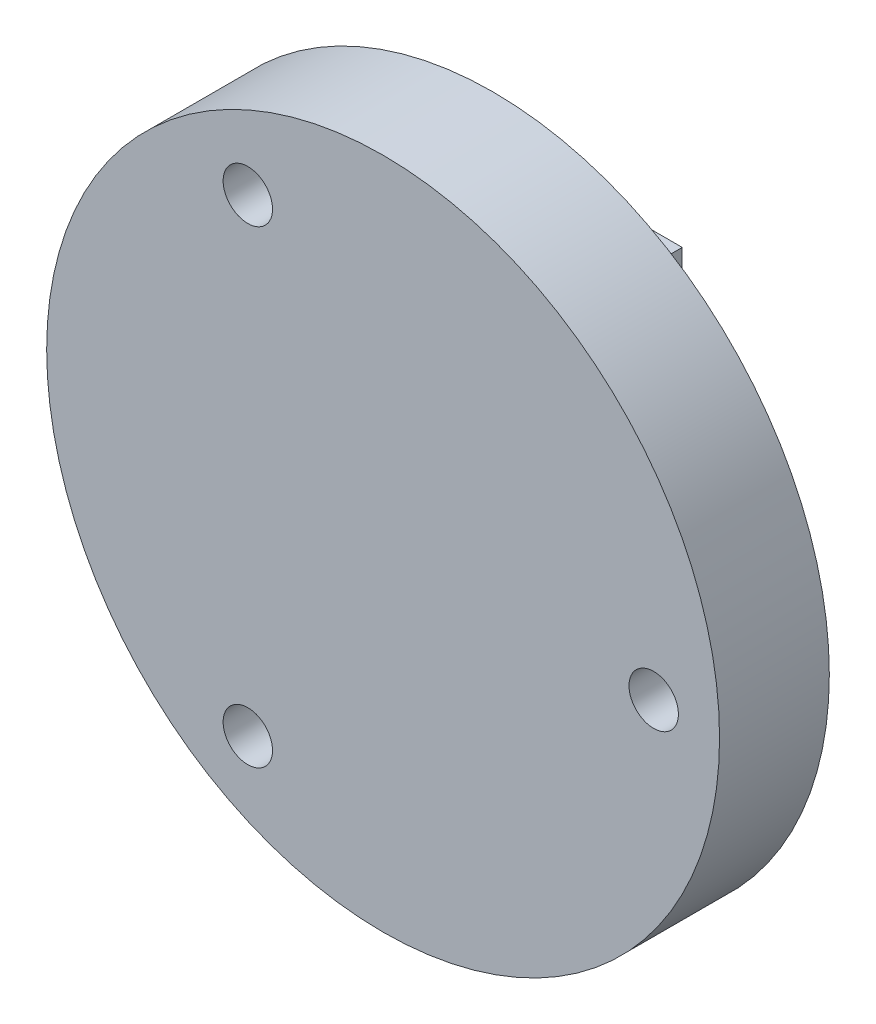
SolidWorks part; units mm, degrees
ref_plane "Спереди" through (0, 0, 0) normal (0, 0, 1) x (1, 0, 0)
ref_plane "Сверху" through (0, 0, 0) normal (0, 1, 0) x (1, 0, 0)
ref_plane "Справа" through (0, 0, 0) normal (1, 0, 0) x (0, 0, -1)
sketch "Эскиз основы" plane through (0, 0, 0) normal (0, 0, 1) x (1, 0, 0)
  line L0 (0, 0) -> (24.65, 0) construction
  line L1 (0, 0) -> (30.65, 0) construction
  line L2 (5.25, -15) -> (-5.25, -15)
  line L3 (5.25, -15) -> (5.25, 15)
  line L4 (5.25, 15) -> (-5.25, 15)
  line L5 (-5.25, -15) -> (-5.25, 15)
  line L6 (5.25, -15) -> (-5.25, 15) construction
  line L7 (5.25, 15) -> (-5.25, -15) construction
  circle A0 centre (0, 0) radius 30.65
  circle A2 centre (0, 0) radius 24.65
  circle A3 centre (24.65, 0) radius 2.25
  circle A4 centre (24.65, 0) radius 3.55
  circle A5 centre (-12.325, -21.3475) radius 3.55
  circle A6 centre (-12.325, -21.3475) radius 2.25
  circle A7 centre (-12.325, 21.3475) radius 3.55
  circle A8 centre (-12.325, 21.3475) radius 2.25
  point P14 (0, 0)
  point P18 (0, 0)
  dimension "D1" = 10.5
  dimension "D2" = 61.3
  dimension "D3" = 49.3
  dimension "D4" = 7.1
  dimension "D5" = 4.5
  dimension "D6" = 24.65
  dimension "D8" = 30
  dimension "D7" = 3
extrude "Основа" add sketch "Эскиз основы" along normal blind 10 contours A0 A7 A2 A4 A5 | A8 A2 A7 | A2 A4 A3 | A2 A4 A3 | A6 A2 A5 | A6 A2 A5 | A7 A2 A5 A4 L2 L5 L4 L3 | L5 L2 L3 L4 | A8 A2 A7 region at (0, 0, 0) region at (-29.7831, 0, 0) region at (22.3212, 0, 0) region at (24.5594, 2.9047, 0) region at (20.4046, 0, 0) region at (-8.9455, 22.1237, 0) region at (-9.7668, 22.7276, 0) region at (-14.0564, -24.3463, 0) region at (-9.6998, -22.5716, 0)
extrude "Отверстия" cut sketch "Эскиз1<3>" along normal blind 5 contours A8 A2 A7 | A8 A2 A7 | A2 A4 A3 | A2 A4 A3 | A6 A2 A5 | A6 A2 A5 region at (22.3212, 0, 0) region at (24.5594, 2.9047, 0) region at (-8.9455, 22.1237, 0) region at (-9.7668, 22.7276, 0) region at (-14.0564, -24.3463, 0) region at (-9.6998, -22.5716, 0)
sketch "Эскиз1<3>" plane through (0, 0, 0) normal (0, 0, 1) x (1, 0, 0) same geometry as "Эскиз основы"
extrude "Бобышка-Вытянуть2" add sketch "Эскиз1<5>" against normal blind 12 contours L5 L2 L3 L4 region at (0, 0, 0)
sketch "Эскиз1<5>" plane through (0, 0, 0) normal (0, 0, 1) x (1, 0, 0) same geometry as "Эскиз основы"
sketch "Эскиз отв под схват" plane through (-5.25, 0, 0) normal (-1, 0, 0) x (0, 0, 1)
  line L0 (-5, 15) -> (-5, -15) construction
  line L1 (-12, 15) -> (0, 15) construction
  line L2 (-12, -15) -> (0, -15) construction
  line L3 (0, -15) -> (0, 15) construction
  line L4 (-12, 0) -> (0, 0) construction
  line L5 (-12, -15) -> (-12, 15) construction
  circle A0 centre (-5, 7.5) radius 2.15
  circle A1 centre (-5, -7.5) radius 2.15
  dimension "D2" = 7.5
  dimension "D3" = 4.3
  dimension "D1" = 5
extrude "Отверстия под схват" cut sketch "Эскиз отв под схват" against normal up to next contours A0 | A1 region at (-5.25, 7.5, -5) region at (-5.25, -7.5, -5)
